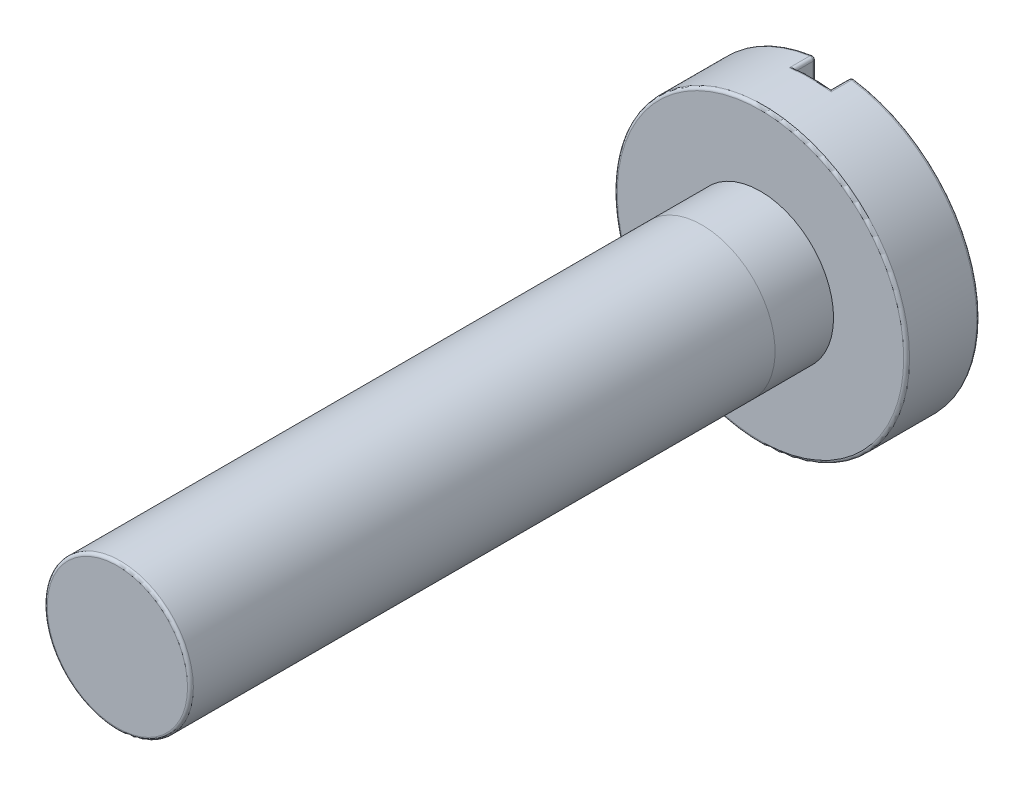
SolidWorks part; units mm, degrees
ref_plane "Front Plane" through (0, 0, 0) normal (0, 0, 1) x (1, 0, 0)
ref_plane "Top Plane" through (0, 0, 0) normal (0, 1, 0) x (1, 0, 0)
ref_plane "Right Plane" through (0, 0, 0) normal (1, 0, 0) x (0, 0, -1)
sketch "Sketch1" plane through (0, 0, 0) normal (0, 0, 1) x (1, 0, 0)
  circle A0 centre (0, 0) radius 1.25
  dimension "D1" = 2.5
extrude "Boss-Extrude1" add sketch "Sketch1" along normal blind 11 contours A0
sketch "Sketch2" plane through (0, 0, 0) normal (0, 0, 1) x (1, 0, 0)
  circle A2 centre (0, 0) radius 2.5
  circle A3 centre (0, 0) radius 2.5
  dimension "D1" = 1.25
extrude "Boss-Extrude2" add sketch "Sketch2" against normal blind 1.25
sketch "Sketch3" plane through (0, 0, -1.25) normal (0, 0, -1) x (-1, 0, 0)
  line L1 (-0.3, 4.1838) -> (0.3, 4.1838)
  line L2 (-0.3, 4.1838) -> (-0.3, -4.1838)
  line L3 (-0.3, -4.1838) -> (0.3, -4.1838)
  line L4 (0.3, 4.1838) -> (0.3, -4.1838)
  line L5 (-0.3, 4.1838) -> (0.3, -4.1838) construction
  line L6 (-0.3, -4.1838) -> (0.3, 4.1838) construction
  point P0 (0, 0)
  dimension "D1" = 0.6
extrude "Cut-Extrude1" cut sketch "Sketch3" against normal blind 0.35
fillet "Fillet1" radius 0.05 12 edges at (1.25, 0, 11) (2.5, 0, 0) (-0.3, -2.4819, -1.075) (0, -2.5, -0.9) (0.3, -2.4819, -1.075) (-0.3, 2.4819, -1.075) (0, 2.5, -0.9) (0.3, 2.4819, -1.075) (0.3, 0, -1.25) (2.5, 0, -1.25) (-2.5, 0, -1.25) (-0.3, 0, -1.25)
sketch "Sketch4" plane through (0, 0, 0) normal (0, 1, 0) x (1, 0, 0)
  line L0 (-4.2772, -1) -> (4.7645, -1)
  line L1 (-1.2, -11) -> (1.2, -11) construction
  dimension "D1" = 10
split line "Split Line1"
